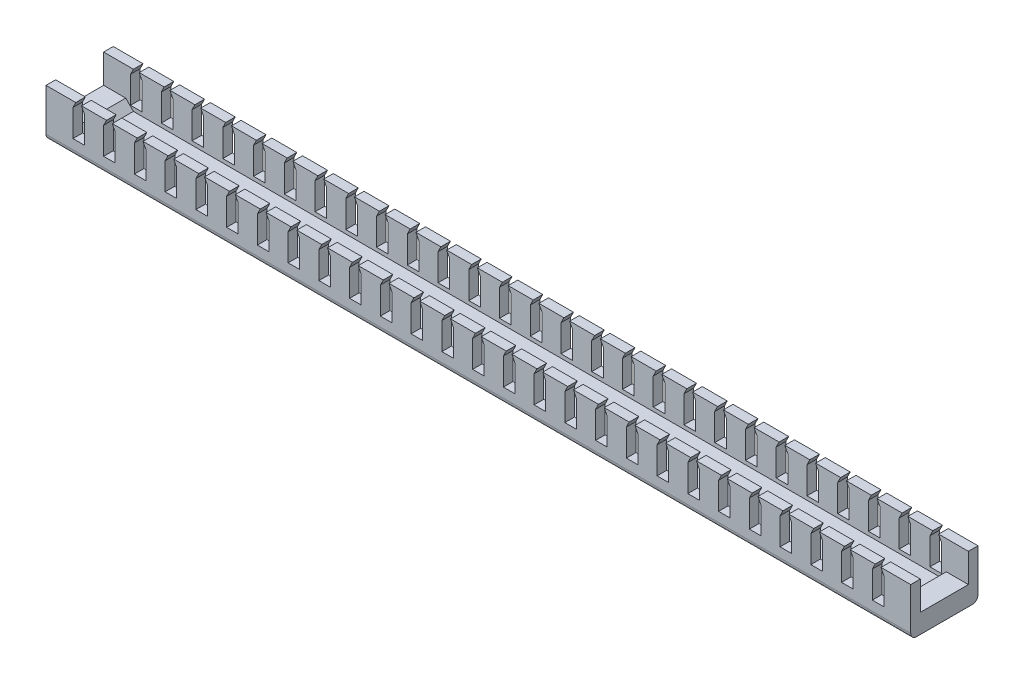
SolidWorks part; units mm, degrees
ref_plane "Front Plane" through (0, 0, 0) normal (0, 0, 1) x (1, 0, 0)
ref_plane "Top Plane" through (0, 0, 0) normal (0, 1, 0) x (1, 0, 0)
ref_plane "Right Plane" through (0, 0, 0) normal (1, 0, 0) x (0, 0, -1)
sketch "Sketch2" plane through (0, 0, 0) normal (1, 0, 0) x (0, 0, -1)
  line L0 (1.5, 0) -> (16, 0)
  line L1 (17.5, 1.5) -> (17.5, 12.5)
  line L2 (17.5, 12.5) -> (15, 12.5)
  line L3 (15, 12.5) -> (15, 3)
  line L4 (15, 3) -> (2.5, 3)
  line L5 (2.5, 3) -> (2.5, 12.5)
  line L6 (2.5, 12.5) -> (0, 12.5)
  line L7 (0, 12.5) -> (0, 1.5)
  arc A0 (16, 0) -> (17.5, 1.5) centre (16, 1.5) ccw
  arc A1 (1.5, 0) -> (0, 1.5) centre (1.5, 1.5) cw
  point P11 (17.5, 0)
  point P14 (0, 0)
  dimension "D5" = 1.5
  dimension "D1" = 12.5
  dimension "D2" = 3
  dimension "D3" = 17.5
  dimension "D4" = 2.5
extrude "ProfileBoss-Extrude1" add sketch "Sketch2" along normal blind 225
sketch "Sketch3" plane through (0, 0, 0) normal (0, 0, 1) x (1, 0, 0)
  line L0 (7.75, 12.5) -> (7, 11)
  line L1 (7, 11) -> (7, 4)
  line L2 (7, 4) -> (10, 4)
  line L3 (10, 4) -> (10, 11)
  line L4 (10, 11) -> (9.25, 12.5)
  line L5 (225, 12.5) -> (0, 12.5) construction
  line L6 (9.25, 12.5) -> (7.75, 12.5)
  line L7 (225, 0) -> (0, 0) construction
  line L8 (0, 12.5) -> (0, 1.5) construction
  line L9 (15.75, 12.5) -> (15, 11)
  line L10 (15, 11) -> (15, 4)
  line L11 (15, 4) -> (18, 4)
  line L12 (18, 4) -> (18, 11)
  line L13 (18, 11) -> (17.25, 12.5)
  line L14 (17.25, 12.5) -> (15.75, 12.5)
  line L15 (23.75, 12.5) -> (23, 11)
  line L16 (23, 11) -> (23, 4)
  line L17 (23, 4) -> (26, 4)
  line L18 (26, 4) -> (26, 11)
  line L19 (26, 11) -> (25.25, 12.5)
  line L20 (25.25, 12.5) -> (23.75, 12.5)
  line L21 (31.75, 12.5) -> (31, 11)
  line L22 (31, 11) -> (31, 4)
  line L23 (31, 4) -> (34, 4)
  line L24 (34, 4) -> (34, 11)
  line L25 (34, 11) -> (33.25, 12.5)
  line L26 (33.25, 12.5) -> (31.75, 12.5)
  line L27 (39.75, 12.5) -> (39, 11)
  line L28 (39, 11) -> (39, 4)
  line L29 (39, 4) -> (42, 4)
  line L30 (42, 4) -> (42, 11)
  line L31 (42, 11) -> (41.25, 12.5)
  line L32 (41.25, 12.5) -> (39.75, 12.5)
  line L33 (47.75, 12.5) -> (47, 11)
  line L34 (47, 11) -> (47, 4)
  line L35 (47, 4) -> (50, 4)
  line L36 (50, 4) -> (50, 11)
  line L37 (50, 11) -> (49.25, 12.5)
  line L38 (49.25, 12.5) -> (47.75, 12.5)
  line L39 (55.75, 12.5) -> (55, 11)
  line L40 (55, 11) -> (55, 4)
  line L41 (55, 4) -> (58, 4)
  line L42 (58, 4) -> (58, 11)
  line L43 (58, 11) -> (57.25, 12.5)
  line L44 (57.25, 12.5) -> (55.75, 12.5)
  line L45 (63.75, 12.5) -> (63, 11)
  line L46 (63, 11) -> (63, 4)
  line L47 (63, 4) -> (66, 4)
  line L48 (66, 4) -> (66, 11)
  line L49 (66, 11) -> (65.25, 12.5)
  line L50 (65.25, 12.5) -> (63.75, 12.5)
  line L51 (71.75, 12.5) -> (71, 11)
  line L52 (71, 11) -> (71, 4)
  line L53 (71, 4) -> (74, 4)
  line L54 (74, 4) -> (74, 11)
  line L55 (74, 11) -> (73.25, 12.5)
  line L56 (73.25, 12.5) -> (71.75, 12.5)
  line L57 (79.75, 12.5) -> (79, 11)
  line L58 (79, 11) -> (79, 4)
  line L59 (79, 4) -> (82, 4)
  line L60 (82, 4) -> (82, 11)
  line L61 (82, 11) -> (81.25, 12.5)
  line L62 (81.25, 12.5) -> (79.75, 12.5)
  line L63 (87.75, 12.5) -> (87, 11)
  line L64 (87, 11) -> (87, 4)
  line L65 (87, 4) -> (90, 4)
  line L66 (90, 4) -> (90, 11)
  line L67 (90, 11) -> (89.25, 12.5)
  line L68 (89.25, 12.5) -> (87.75, 12.5)
  line L69 (95.75, 12.5) -> (95, 11)
  line L70 (95, 11) -> (95, 4)
  line L71 (95, 4) -> (98, 4)
  line L72 (98, 4) -> (98, 11)
  line L73 (98, 11) -> (97.25, 12.5)
  line L74 (97.25, 12.5) -> (95.75, 12.5)
  line L75 (103.75, 12.5) -> (103, 11)
  line L76 (103, 11) -> (103, 4)
  line L77 (103, 4) -> (106, 4)
  line L78 (106, 4) -> (106, 11)
  line L79 (106, 11) -> (105.25, 12.5)
  line L80 (105.25, 12.5) -> (103.75, 12.5)
  line L81 (111.75, 12.5) -> (111, 11)
  line L82 (111, 11) -> (111, 4)
  line L83 (111, 4) -> (114, 4)
  line L84 (114, 4) -> (114, 11)
  line L85 (114, 11) -> (113.25, 12.5)
  line L86 (113.25, 12.5) -> (111.75, 12.5)
  line L87 (119.75, 12.5) -> (119, 11)
  line L88 (119, 11) -> (119, 4)
  line L89 (119, 4) -> (122, 4)
  line L90 (122, 4) -> (122, 11)
  line L91 (122, 11) -> (121.25, 12.5)
  line L92 (121.25, 12.5) -> (119.75, 12.5)
  line L93 (127.75, 12.5) -> (127, 11)
  line L94 (127, 11) -> (127, 4)
  line L95 (127, 4) -> (130, 4)
  line L96 (130, 4) -> (130, 11)
  line L97 (130, 11) -> (129.25, 12.5)
  line L98 (129.25, 12.5) -> (127.75, 12.5)
  line L99 (135.75, 12.5) -> (135, 11)
  line L100 (135, 11) -> (135, 4)
  line L101 (135, 4) -> (138, 4)
  line L102 (138, 4) -> (138, 11)
  line L103 (138, 11) -> (137.25, 12.5)
  line L104 (137.25, 12.5) -> (135.75, 12.5)
  line L105 (143.75, 12.5) -> (143, 11)
  line L106 (143, 11) -> (143, 4)
  line L107 (143, 4) -> (146, 4)
  line L108 (146, 4) -> (146, 11)
  line L109 (146, 11) -> (145.25, 12.5)
  line L110 (145.25, 12.5) -> (143.75, 12.5)
  line L111 (151.75, 12.5) -> (151, 11)
  line L112 (151, 11) -> (151, 4)
  line L113 (151, 4) -> (154, 4)
  line L114 (154, 4) -> (154, 11)
  line L115 (154, 11) -> (153.25, 12.5)
  line L116 (153.25, 12.5) -> (151.75, 12.5)
  line L117 (159.75, 12.5) -> (159, 11)
  line L118 (159, 11) -> (159, 4)
  line L119 (159, 4) -> (162, 4)
  line L120 (162, 4) -> (162, 11)
  line L121 (162, 11) -> (161.25, 12.5)
  line L122 (161.25, 12.5) -> (159.75, 12.5)
  line L123 (167.75, 12.5) -> (167, 11)
  line L124 (167, 11) -> (167, 4)
  line L125 (167, 4) -> (170, 4)
  line L126 (170, 4) -> (170, 11)
  line L127 (170, 11) -> (169.25, 12.5)
  line L128 (169.25, 12.5) -> (167.75, 12.5)
  line L129 (175.75, 12.5) -> (175, 11)
  line L130 (175, 11) -> (175, 4)
  line L131 (175, 4) -> (178, 4)
  line L132 (178, 4) -> (178, 11)
  line L133 (178, 11) -> (177.25, 12.5)
  line L134 (177.25, 12.5) -> (175.75, 12.5)
  line L135 (183.75, 12.5) -> (183, 11)
  line L136 (183, 11) -> (183, 4)
  line L137 (183, 4) -> (186, 4)
  line L138 (186, 4) -> (186, 11)
  line L139 (186, 11) -> (185.25, 12.5)
  line L140 (185.25, 12.5) -> (183.75, 12.5)
  line L141 (191.75, 12.5) -> (191, 11)
  line L142 (191, 11) -> (191, 4)
  line L143 (191, 4) -> (194, 4)
  line L144 (194, 4) -> (194, 11)
  line L145 (194, 11) -> (193.25, 12.5)
  line L146 (193.25, 12.5) -> (191.75, 12.5)
  line L147 (199.75, 12.5) -> (199, 11)
  line L148 (199, 11) -> (199, 4)
  line L149 (199, 4) -> (202, 4)
  line L150 (202, 4) -> (202, 11)
  line L151 (202, 11) -> (201.25, 12.5)
  line L152 (201.25, 12.5) -> (199.75, 12.5)
  line L153 (207.75, 12.5) -> (207, 11)
  line L154 (207, 11) -> (207, 4)
  line L155 (207, 4) -> (210, 4)
  line L156 (210, 4) -> (210, 11)
  line L157 (210, 11) -> (209.25, 12.5)
  line L158 (209.25, 12.5) -> (207.75, 12.5)
  line L159 (215.75, 12.5) -> (215, 11)
  line L160 (215, 11) -> (215, 4)
  line L161 (215, 4) -> (218, 4)
  line L162 (218, 4) -> (218, 11)
  line L163 (218, 11) -> (217.25, 12.5)
  line L164 (217.25, 12.5) -> (215.75, 12.5)
  line L255 (225, 12.5) -> (225, 1.5) construction
  point P12 (218, 7.5)
  dimension "D1" = 3
  dimension "D2" = 1.5
  dimension "D3" = 4
  dimension "D5" = 7
  dimension "D4" = 1.5
  dimension "D7" = 225
  dimension "D8" = 5
  dimension "D9" = 7
  dimension "D6" = 27
extrude "SpikesCut-Extrude1" cut sketch "Sketch3" against normal through all
sketch "MountHoleThicknessSketch4" plane through (0, 3, 0) normal (0, 1, 0) x (1, 0, 0)
  line L0 (0, 15) -> (0, 2.5) construction
  line L1 (0, 15) -> (7.75, 15)
  line L2 (0, 15) -> (0, 2.5)
  line L3 (0, 2.5) -> (7.75, 2.5)
  line L4 (7.75, 15) -> (7.75, 2.5)
  line L5 (225, 2.5) -> (0, 2.5) construction
  line L6 (7.75, 15) -> (0, 15) construction
  line L7 (7, 2.5) -> (10, 2.5) construction
  line L8 (7.75, 2.5) -> (7.75, 0) construction
  line L10 (225, 15) -> (217.25, 15)
  line L11 (225, 15) -> (225, 2.5)
  line L12 (225, 2.5) -> (217.25, 2.5)
  line L13 (217.25, 15) -> (217.25, 2.5)
extrude "MountHolesThicknessBoss-Extrude1" add sketch "MountHoleThicknessSketch4" along normal blind 2
sketch "MountHolesSketch5" plane through (0, 3, 0) normal (0, 1, 0) x (1, 0, 0)
  line L0 (0, 15) -> (0, 2.5) construction
  line L1 (225, 15) -> (225, 2.5) construction
  line L2 (7.75, 0) -> (0, 0) construction
  circle A0 centre (5, 7.5) radius 2.05
  circle A1 centre (220, 7.5) radius 2.05
  point P11 (3.875, 0)
  dimension "D1" = 4.1
  dimension "D2" = 5
  dimension "D3" = 5
  dimension "D4" = 7.5
  dimension "D5" = 215
extrude "MountHolesCut-Extrude2" cut sketch "MountHolesSketch5" against normal blind 4
chamfer "Chamfer1" distance 2 angle 45 2 edges at (217.25, 5, -8.75) (7.75, 5, -8.75)
equation "\"SerratedChannelWidth\"= 17.5"
equation "\"D3@Sketch2\"=\"SerratedChannelWidth\""
equation "\"SerratedChannelHeight\"= 12.5mm"
equation "\"D1@Sketch2\"=\"SerratedChannelHeight\""
equation "\"SerratedChannelBaseHeight\"= 3mm"
equation "\"D2@Sketch2\"=\"SerratedChannelBaseHeight\""
equation "\"SerratedChannelChannelProngWidth\"= 2.5mm"
equation "\"D4@Sketch2\"=\"SerratedChannelChannelProngWidth\""
equation "\"SerratedChannelLength\"= 225mm"
equation "\"D1@ProfileBoss-Extrude1\"=\"SerratedChannelLength\""
equation "\"SerratedChannelProngOpenningWidth\"= 3mm"
equation "\"D1@Sketch3\"=\"SerratedChannelProngOpenningWidth\""
equation "\"SerratedChannelProngBaseHeight\"= 4mm"
equation "\"D3@Sketch3\"=\"SerratedChannelProngBaseHeight\""
equation "\"SerratedChannelProngHookSize\"= 1.5mm"
equation "\"D4@Sketch3\"=\"SerratedChannelProngHookSize\""
equation "\"D2@Sketch3\"=\"SerratedChannelProngHookSize\""
equation "\"SerratedChannelProngClosedWidth\"= 5mm"
equation "\"D8@Sketch3\"=\"SerratedChannelProngClosedWidth\""
equation "\"SerratedChannelStartOffset\"=7"
equation "\"M3HeatInsertHoleDepth\"= 4mm"
equation "\"M3HeatInsertHoleDiameter\"= 4mm + .1mm'Add .1mm for printing"
equation "\"D1@MountHolesCut-Extrude2\"=\"M3HeatInsertHoleDepth\""
equation "\"D1@MountHolesSketch5\"=\"M3HeatInsertHoleDiameter\""
